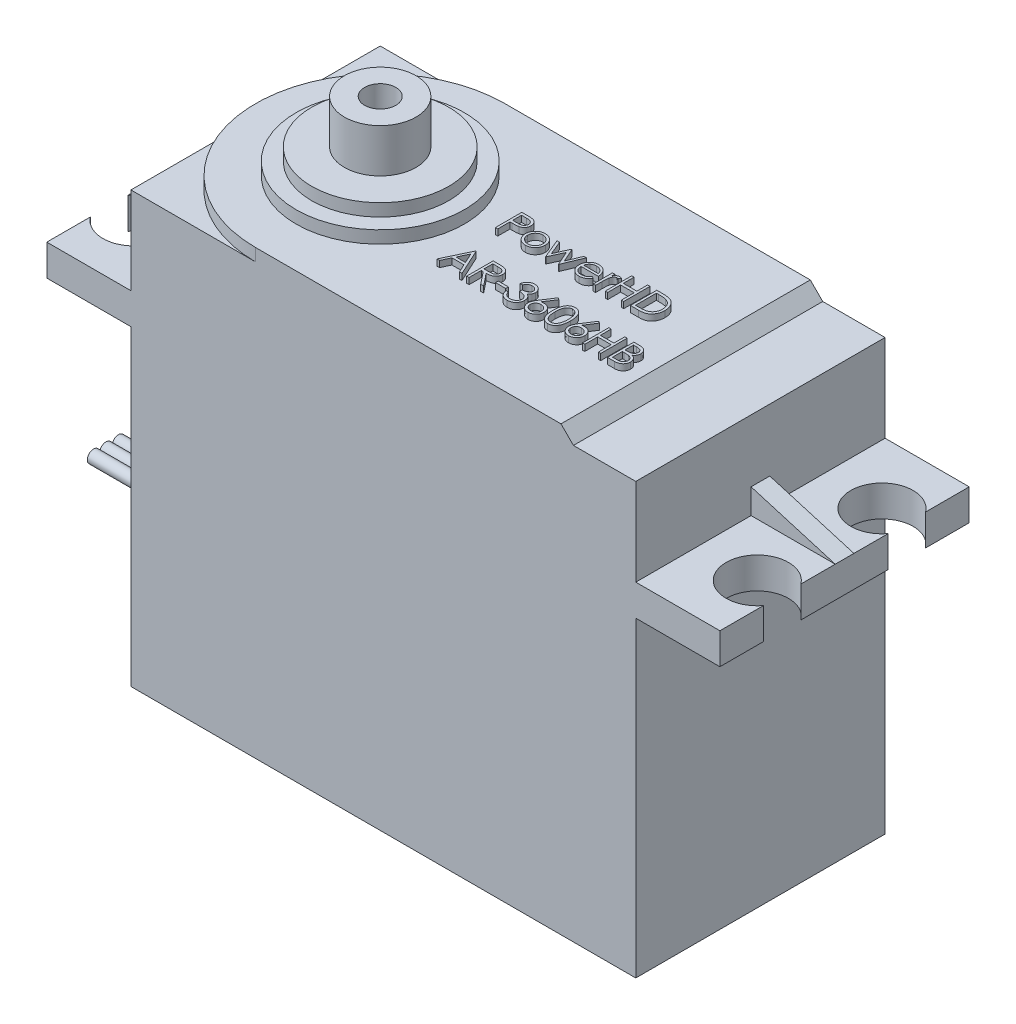
SolidWorks part; units mm, degrees
ref_plane "Ön Düzlem" through (0, 0, 0) normal (0, 0, 1) x (1, 0, 0)
ref_plane "Üst Düzlem" through (0, 0, 0) normal (0, 1, 0) x (1, 0, 0)
ref_plane "Sağ Düzlem" through (0, 0, 0) normal (1, 0, 0) x (0, 0, -1)
sketch "Çizim1" plane through (0, 0, 0) normal (0, 0, 1) x (1, 0, 0)
  line L0 (0, 0) -> (0, 26)
  line L1 (0, 26) -> (-6.75, 26)
  line L2 (-6.75, 26) -> (-6.75, 28.5)
  line L3 (-6.75, 28.5) -> (0, 28.5)
  line L4 (0, 28.5) -> (0, 35.5)
  line L5 (0, 35.5) -> (40.5, 35.5)
  line L6 (40.5, 35.5) -> (40.5, 28.5)
  line L7 (40.5, 28.5) -> (47.25, 28.5)
  line L8 (47.25, 28.5) -> (47.25, 26)
  line L9 (47.25, 26) -> (40.5, 26)
  line L10 (40.5, 26) -> (40.5, 0)
  line L11 (40.5, 0) -> (0, 0)
  dimension "D1" = 2.5
  dimension "D2" = 2.5
  dimension "D3" = 35.5
  dimension "D4" = 40.5
  dimension "D5" = 7
  dimension "D6" = 7
  dimension "D8" = 54
extrude "Yükseklik-Ekstrüzyon1" add sketch "Çizim1" along normal blind 20
sketch "Çizim2" plane through (0, 35.5, 0) normal (0, 1, 0) x (1, 0, 0)
  line L0 (0, -20) -> (0, 0) construction
  line L1 (40.5, 0) -> (0, 0) construction
  line L2 (35.5, 0) -> (35.5, -20)
  line L3 (40.5, -20) -> (0, -20) construction
  line L4 (40.5, -20) -> (40.5, 0) construction
  line L5 (35.5, 0) -> (10, 0)
  line L6 (35.5, -20) -> (10, -20)
  arc A0 (10, 0) -> (10, -20) centre (10, -10) ccw
  dimension "D1" = 20
  dimension "D2" = 5
extrude "Yükseklik-Ekstrüzyon2" add sketch "Çizim2" along normal blind 1
sketch "Çizim3" plane through (0, 36.5, 0) normal (0, 1, 0) x (1, 0, 0)
  circle A0 centre (10, -10) radius 6.75
  dimension "D1" = 13.5
extrude "Yükseklik-Ekstrüzyon3" add sketch "Çizim3" along normal blind 1
sketch "Çizim4" plane through (0, 37.5, 0) normal (0, 1, 0) x (1, 0, 0)
  circle A0 centre (10, -10) radius 5.5
  dimension "D1" = 11
extrude "Yükseklik-Ekstrüzyon4" add sketch "Çizim4" along normal blind 1
sketch "Çizim5" plane through (0, 38.5, 0) normal (0, 1, 0) x (1, 0, 0)
  circle A0 centre (10, -10) radius 2.875
  circle A1 centre (10, -10) radius 1.25
  dimension "D1" = 5.75
  dimension "D2" = 2.5
extrude "Yükseklik-Ekstrüzyon5" add sketch "Çizim5" along normal blind 3.5
sketch "Çizim6" plane through (0, 0, 20) normal (0, 0, 1) x (1, 0, 0)
  line L0 (35.5, 35.5) -> (35.5, 36.5)
  line L1 (35.5, 36.5) -> (34.5, 36.5)
  line L2 (10, 36.5) -> (35.5, 36.5) construction
  line L3 (34.5, 36.5) -> (35.5, 35.5)
  dimension "D1" = 1
extrude "Kes-Ekstrüzyon1" cut sketch "Çizim6" against normal through all
sketch "Çizim7" plane through (0, 28.5, 0) normal (0, 1, 0) x (1, 0, 0)
  line L0 (-6.75, -20) -> (-6.75, 0) construction
  line L1 (20.25, 12.0535) -> (20.25, -28.4025) construction
  circle A0 centre (-4.75, -5) radius 2.5
  circle A1 centre (-4.75, -15) radius 2.5
  circle A2 centre (45.25, -15) radius 2.5
  circle A3 centre (45.25, -5) radius 2.5
  point P0 (-6.75, -10)
  point P13 (47.25, -10)
  dimension "D5" = 5
  dimension "D6" = 5
  dimension "D1" = 5
  dimension "D2" = 5
  dimension "D3" = 2
  dimension "D4" = 2
  dimension "D7" = 27
extrude "Kes-Ekstrüzyon2" cut sketch "Çizim7" against normal blind 3.5
ref_plane "Düzlem1" through (0, 0, 10) normal (0, 0, 1) x (1, 0, 0)
sketch "Çizim12" plane through (0, 0, 10) normal (0, 0, 1) x (1, 0, 0)
  line L0 (-6.75, 28.5) -> (0, 30.5)
  line L3 (0, 35.5) -> (0, 28.5) construction
  line L5 (10, 35.5) -> (0, 35.5) construction
  line L6 (0, 28.5) -> (-6.75, 28.5) construction
  dimension "D2" = 5
rib "Feder14" sketch "Çizim12" sketch "Çizim12" thickness 1.5 extrusion direction parallel to sketch draft on no parameters "D1"=1.5
sketch "Çizim13" plane through (0, 0, 10) normal (0, 0, 1) x (1, 0, 0)
  line L0 (47.25, 28.5) -> (40.5, 30.5)
  line L1 (40.5, 28.5) -> (40.5, 35.5) construction
  line L2 (40.5, 35.5) -> (35.5, 35.5) construction
  dimension "D1" = 5
rib "Feder16" sketch "Çizim13" sketch "Çizim13" thickness 1.5 extrusion direction parallel to sketch draft on no parameters "D1"=1.5
sketch "Çizim14" plane through (0, 0, 0) normal (-1, 0, 0) x (0, 0, 1)
  line L0 (20, 0) -> (0, 0) construction
  circle A0 centre (10, 15) radius 2.25
  dimension "D1" = 4.5
  dimension "D2" = 15
extrude "Kes-Ekstrüzyon3" cut sketch "Çizim14" against normal blind 7
sketch "Çizim15" plane through (0, 0, 0) normal (-1, 0, 0) x (0, 0, 1)
  line L0 (0, 26) -> (0, 0) construction
  line L1 (6.5, 8) -> (13.5, 8)
  line L2 (6.5, 8) -> (6.5, 5)
  line L3 (6.5, 5) -> (13.5, 5)
  line L4 (13.5, 8) -> (13.5, 5)
  line L5 (20, 0) -> (0, 0) construction
  dimension "D1" = 7
  dimension "D2" = 3
  dimension "D3" = 6.5
  dimension "D4" = 5
extrude "Yükseklik-Ekstrüzyon6" add sketch "Çizim15" along normal blind 6
sketch "Çizim16" plane through (-6, 0, 0) normal (-1, 0, 0) x (0, 0, 1)
  line L2 (6.5, 8) -> (6.5, 5) construction
  line L3 (6.5, 5) -> (13.5, 5) construction
  circle A0 centre (9, 6.5) radius 0.5
  circle A1 centre (10, 6.5) radius 0.5
  circle A2 centre (11, 6.5) radius 0.5
  point P10 (8.5, 6.5)
  dimension "D1" = 1
  dimension "D2" = 2
  dimension "D3" = 1.5
extrude "Yükseklik-Ekstrüzyon8" add sketch "Çizim16" along normal blind 6 separate body contours A0 | A1 | A2 region at (-6, 6.5, 9) region at (-6, 6.5, 10)
chamfer "Pah1" distance 1 angle 45 4 edges at (0, 0, 10) (20.25, 0, 20) (40.5, 0, 10) (20.25, 0, 0)
sketch "Çizim17" plane through (0, 36.5, 0) normal (0, 1, 0) x (1, 0, 0)
  text T0 "PowerHD \r\nAR-3606HB" font "Century Gothic" height in points 8
extrude "Yükseklik-Ekstrüzyon9" add sketch "Çizim17" along normal blind 0.5
